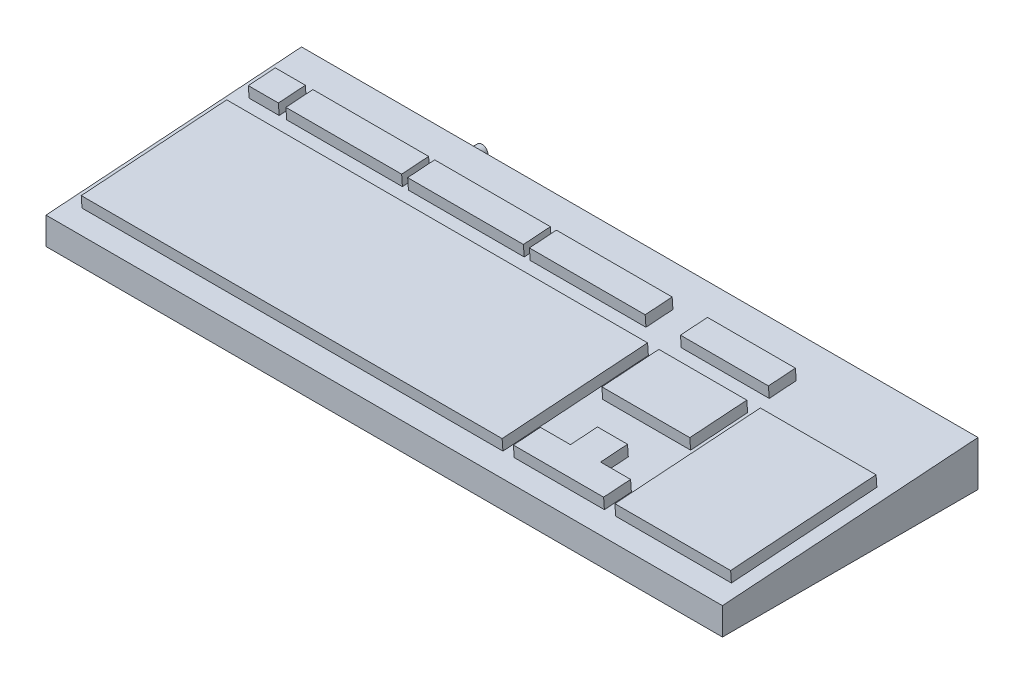
SolidWorks part; units mm, degrees
ref_plane "Front Plane" through (0, 0, 0) normal (0, 0, 1) x (1, 0, 0)
ref_plane "Top Plane" through (0, 0, 0) normal (0, 1, 0) x (1, 0, 0)
ref_plane "Right Plane" through (0, 0, 0) normal (1, 0, 0) x (0, 0, -1)
sketch "Sketch1" plane through (0, 0, 0) normal (0, 1, 0) x (1, 0, 0)
  line L1 (0, 0) -> (450, 0)
  line L2 (0, 0) -> (0, 170)
  line L3 (0, 170) -> (450, 170)
  line L4 (450, 0) -> (450, 170)
  dimension "D1" = 170
  dimension "D2" = 450
extrude "Boss-Extrude1" add sketch "Sketch1" along normal blind 30
chamfer "Chamfer1" distance 170 angle 4 1 edges at (225, 30, 0) first distance on face at (225, 30, -85)
sketch "Sketch2" plane through (0, 0, -170) normal (0, 0, -1) x (-1, 0, 0)
  line L0 (0, 30) -> (0, 0) construction
  line L1 (-450, 30) -> (0, 30) construction
  circle A0 centre (-105, 15) radius 4
  dimension "D3" = 8
  dimension "D1" = 105
  dimension "D2" = 15
extrude "Boss-Extrude2" add sketch "Sketch2" along normal blind 15
sketch "Sketch3" plane through (0, 18.0243, 1.2604) normal (0, 0.9976, 0.0698) x (1, 0, 0)
  line L0 (296.5, 16.2635) -> (356.5, 16.2635)
  line L1 (9, 16.2635) -> (289, 16.2635)
  line L2 (9, 16.2635) -> (9, 113.2635)
  line L3 (9, 113.2635) -> (289, 113.2635)
  line L4 (289, 16.2635) -> (289, 113.2635)
  line L5 (9, 145.6786) -> (29, 145.6786)
  line L6 (9, 145.6786) -> (9, 127.6786)
  line L7 (9, 127.6786) -> (29, 127.6786)
  line L8 (29, 145.6786) -> (29, 127.6786)
  line L9 (34, 145.6786) -> (111, 145.6786)
  line L10 (34, 145.6786) -> (34, 127.6786)
  line L11 (34, 127.6786) -> (111, 127.6786)
  line L12 (111, 145.6786) -> (111, 127.6786)
  line L13 (115, 145.6786) -> (192, 145.6786)
  line L14 (115, 145.6786) -> (115, 127.6786)
  line L15 (115, 127.6786) -> (192, 127.6786)
  line L16 (192, 145.6786) -> (192, 127.6786)
  line L17 (196, 145.6786) -> (273, 145.6786)
  line L18 (196, 145.6786) -> (196, 127.6786)
  line L19 (196, 127.6786) -> (273, 127.6786)
  line L20 (273, 145.6786) -> (273, 127.6786)
  line L21 (296.5, 145.6786) -> (355, 145.6786)
  line L22 (296.5, 145.6786) -> (296.5, 127.6786)
  line L23 (296.5, 127.6786) -> (355, 127.6786)
  line L24 (355, 145.6786) -> (355, 127.6786)
  line L25 (296.5, 113.2635) -> (355, 113.2635)
  line L26 (296.5, 113.2635) -> (296.5, 75.2635)
  line L27 (296.5, 75.2635) -> (355, 75.2635)
  line L28 (355, 113.2635) -> (355, 75.2635)
  line L29 (441, 16.2635) -> (364, 16.2635)
  line L30 (441, 16.2635) -> (441, 113.2635)
  line L31 (441, 113.2635) -> (364, 113.2635)
  line L32 (364, 16.2635) -> (364, 113.2635)
  line L33 (356.5, 16.2635) -> (356.5, 34.2635)
  line L34 (356.5, 34.2635) -> (336.5, 34.2635)
  line L35 (336.5, 34.2635) -> (336.5, 52.2635)
  line L36 (336.5, 52.2635) -> (316.5, 52.2635)
  line L37 (316.5, 52.2635) -> (316.5, 34.2635)
  line L38 (316.5, 34.2635) -> (296.5, 34.2635)
  line L39 (296.5, 34.2635) -> (296.5, 16.2635)
  line L40 (0, 1.2635) -> (0, 171.6786) construction
  line L41 (450, 171.6786) -> (0, 171.6786) construction
  line L42 (450, 1.2635) -> (0, 1.2635) construction
  dimension "D1" = 18
  dimension "D2" = 20
  dimension "D3" = 77
  dimension "D4" = 58.5
  dimension "D5" = 97
  dimension "D6" = 9
  dimension "D7" = 26
  dimension "D8" = 26
  dimension "D9" = 26
  dimension "D10" = 26
  dimension "D11" = 26
  dimension "D12" = 280
  dimension "D13" = 15
  dimension "D14" = 5
  dimension "D15" = 4
  dimension "D16" = 4
  dimension "D17" = 7.5
  dimension "D18" = 7.5
  dimension "D19" = 38
  dimension "D20" = 15
  dimension "D21" = 9
extrude "Boss-Extrude3" add sketch "Sketch3" along normal blind 7.5
